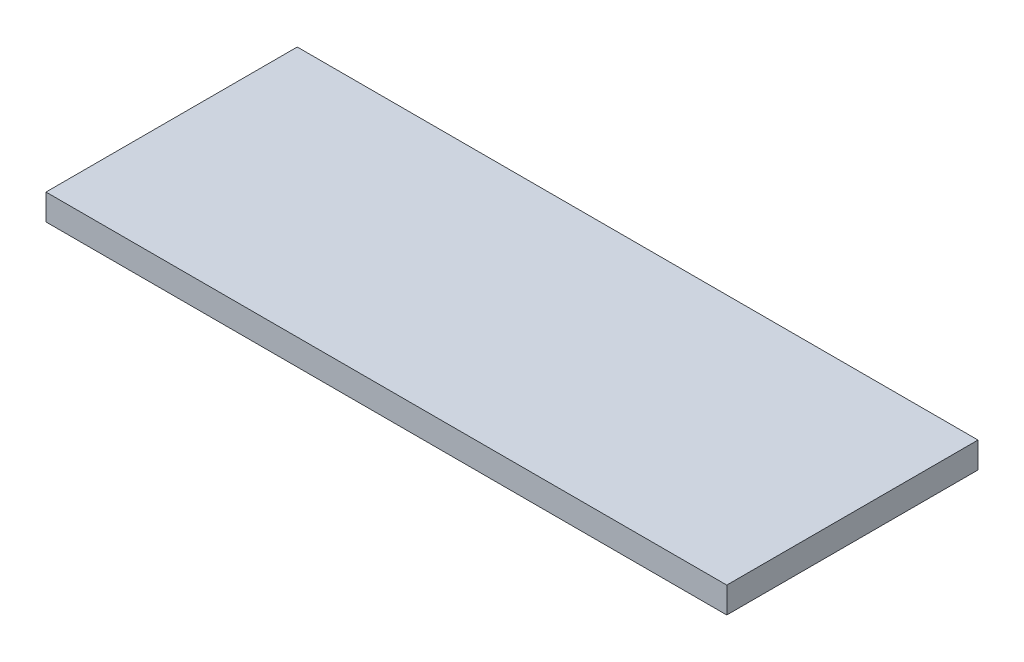
SolidWorks part; units mm, degrees
ref_plane "Front Plane" through (0, 0, 0) normal (0, 0, 1) x (1, 0, 0)
ref_plane "Top Plane" through (0, 0, 0) normal (0, 1, 0) x (1, 0, 0)
ref_plane "Right Plane" through (0, 0, 0) normal (1, 0, 0) x (0, 0, -1)
sketch "Sketch1" plane through (0, 0, 0) normal (0, 1, 0) x (1, 0, 0)
  line L1 (0, 0) -> (42, 0)
  line L2 (0, 0) -> (0, 15.5)
  line L3 (0, 15.5) -> (42, 15.5)
  line L4 (42, 0) -> (42, 15.5)
  dimension "D1" = 15.5
  dimension "D2" = 42
extrude "Boss-Extrude1" add sketch "Sketch1" along normal blind 1.6
